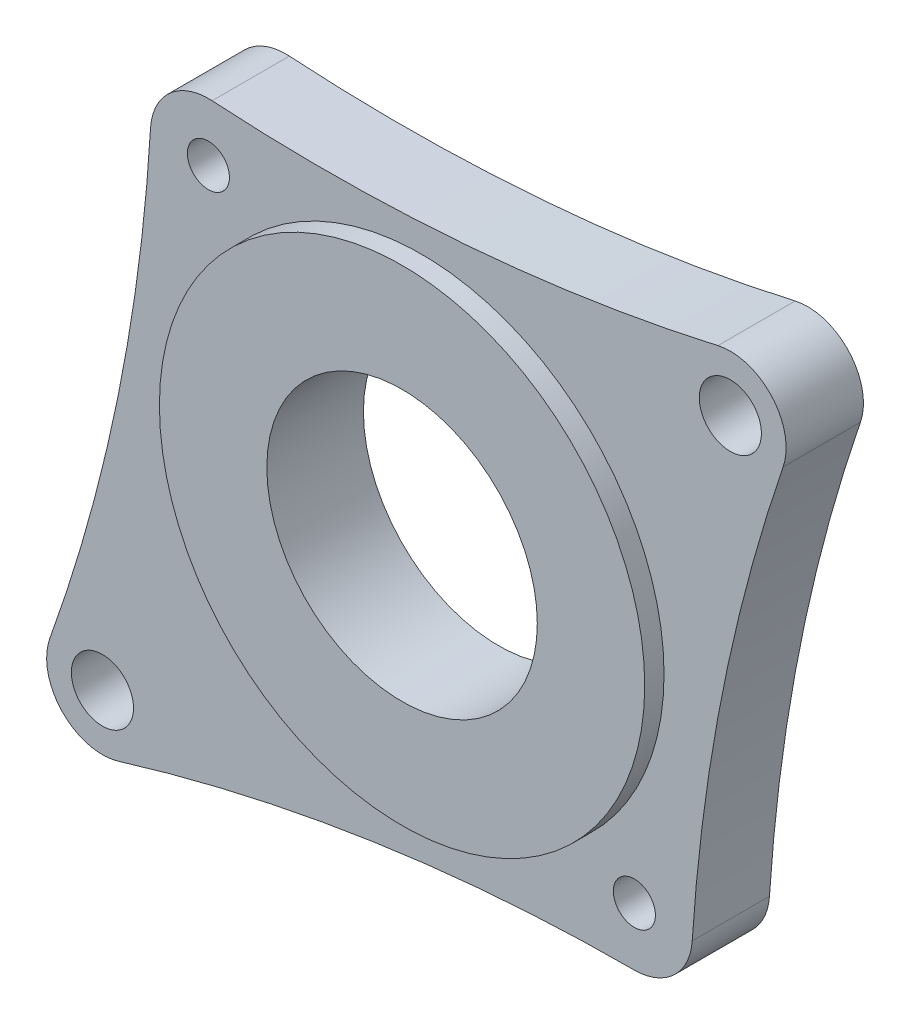
SolidWorks part; units mm, degrees
ref_plane "Front" through (0, 0, 0) normal (0, 0, 1) x (1, 0, 0)
ref_plane "Top" through (0, 0, 0) normal (0, 1, 0) x (1, 0, 0)
ref_plane "Right" through (0, 0, 0) normal (1, 0, 0) x (0, 0, -1)
sketch "Sketch1" plane through (0, 0, 0) normal (0, 0, 1) x (1, 0, 0)
  line L0 (0, -10.3956) -> (0, 10.3956) construction
  line L6 (-17.5, 17.5) -> (-17.1967, 22.2528) construction
  line L9 (17.5, -17.5) -> (17.5, -22.2625) construction
  arc A15 (29.7246, 19.6563) -> (24.3639, 25.6068) centre (25.3858, 21.1374) ccw
  circle A17 centre (25.3858, 21.1374) radius 2.0193 construction
  arc A18 (-30.5229, -22.656) -> (-24.8682, -28.5889) centre (-26.2075, -24.2042) ccw
  circle A19 centre (-26.2075, -24.2042) radius 2.0193 construction
  arc A20 (17.5, -22.2625) -> (22.2525, -17.8083) centre (17.5, -17.5) ccw
  arc A21 (-17.1967, 22.2528) -> (-22.2542, 17.7805) centre (-17.5, 17.5) ccw
  circle A22 centre (17.5, -17.5) radius 2.3479 construction
  circle A23 centre (-17.5, 17.5) radius 2.3479 construction
  arc A24 (-17.1967, 22.2528) -> (24.3639, 25.6068) centre (-7.9615, 166.9916) ccw
  arc A25 (29.7246, 19.6563) -> (22.2525, -17.8083) centre (166.9814, -27.1963) ccw
  arc A26 (17.5, -22.2625) -> (-24.8682, -28.5889) centre (17.5, -167.2956) ccw
  arc A27 (-30.5229, -22.656) -> (-22.2542, 17.7805) centre (-167.0355, 26.3224) ccw
  dimension "D1" = 9.525
  dimension "D2" = 9.1694
extrude "Boss-Extrude1" add sketch "Sketch1" along normal blind 6.35
hole_wizard "7/8 (0.875) Diameter Hole1" positions "Sketch3" profile "Sketch4" hole size "7/8" standard "ANSI Inch" end condition through all
sketch "Sketch3" plane through (0, 0, 6.35) normal (0, 0, 1) x (1, 0, 0)
  point P0 (0, 0)
sketch "Sketch4" plane through (0, 0, 6.35) normal (1, 0, 0) x (0, -1, 0)
  line L0 (0, 0) -> (0, 6.35)
  line L1 (0, 6.35) -> (11.1125, 6.35)
  line L2 (11.1125, 6.35) -> (11.1125, 0)
  line L5 (11.1125, 0) -> (0, 0)
  line L11 (0, -6.35) -> (0, 107.95) construction
  dimension "Thru Hole Dia." = 22.225
  dimension "Thru Hole Depth" = 6.35
hole_wizard "#10 Clearance Hole1" positions "Sketch26" profile "Sketch28" hole size "#10" standard "ANSI Inch" end condition through all
sketch "Sketch26" plane through (0, 0, 6.35) normal (0, 0, 1) x (1, 0, 0)
  arc A2 (29.7246, 19.6563) -> (24.3639, 25.6068) centre (25.3858, 21.1374) ccw construction
  arc A3 (-30.5229, -22.656) -> (-24.8682, -28.5889) centre (-26.2075, -24.2042) ccw construction
  point P0 (25.3858, 21.1374)
  point P2 (-26.2075, -24.2042)
sketch "Sketch28" plane through (25.3858, 21.1374, 6.35) normal (1, 0, 0) x (0, -1, 0)
  line L0 (0, 0) -> (0, 6.35)
  line L1 (0, 6.35) -> (2.5527, 6.35)
  line L2 (2.5527, 6.35) -> (2.5527, 0)
  line L5 (2.5527, 0) -> (0, 0)
  line L11 (0, -6.35) -> (0, 107.95) construction
  dimension "Thru Hole Dia." = 5.1054
  dimension "Thru Hole Depth" = 6.35
hole_wizard "#8-32 Tapped Hole1" positions "Sketch29" profile "Sketch30" tap size "#8-32" standard "ANSI Inch" end condition through all
sketch "Sketch29" plane through (0, 0, 6.35) normal (0, 0, 1) x (1, 0, 0)
  point P0 (17.5, -17.5)
  point P3 (-17.5, 17.5)
sketch "Sketch30" plane through (17.5, -17.5, 6.35) normal (1, 0, 0) x (0, -1, 0)
  line L0 (0, 0) -> (0, 6.35)
  line L1 (0, 6.35) -> (1.7272, 6.35)
  line L2 (1.7272, 6.35) -> (1.7272, 0)
  line L5 (1.7272, 0) -> (0, 0)
  line L11 (0, -6.35) -> (0, 107.95) construction
  dimension "Thru Tap Drill Dia." = 3.4544
  dimension "Thru Tap Drill Depth" = 6.35
cosmetic thread "Hole Thread1" parameters "D2"=4.1656
cosmetic thread "Hole Thread2" parameters "D2"=4.1656
sketch "Sketch33" plane through (0, 0, 6.35) normal (0, 0, 1) x (1, 0, 0)
  circle A0 centre (0, 0) radius 19.939
  circle A1 centre (0, 0) radius 11.1125
  circle A2 centre (0, 0) radius 11.1125 construction
  dimension "D1" = 39.878
extrude "Boss-Extrude3" add sketch "Sketch33" along normal blind 1.5875
sketch "Sketch34" plane through (0, 0, 7.9375) normal (0, 0, 1) x (1, 0, 0)
  circle A0 centre (0, 0) radius 19.05
  circle A1 centre (0, 0) radius 19.939
  circle A2 centre (0, 0) radius 19.939 construction
  dimension "D1" = 38.1
extrude "Cut-Extrude1" [suppressed] cut sketch "Sketch34" against normal blind 0.7937
